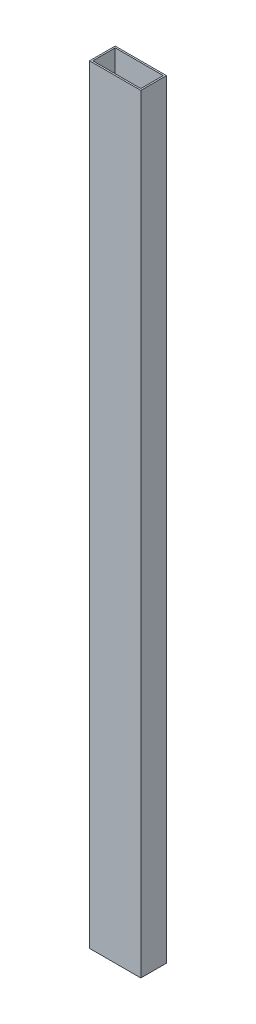
SolidWorks part; units mm, degrees
ref_plane "Front Plane" through (0, 0, 0) normal (0, 0, 1) x (1, 0, 0)
ref_plane "Top Plane" through (0, 0, 0) normal (0, 1, 0) x (1, 0, 0)
ref_plane "Right Plane" through (0, 0, 0) normal (1, 0, 0) x (0, 0, -1)
sketch "Sketch1" plane through (0, 0, 0) normal (0, 1, 0) x (1, 0, 0)
  line L0 (-23.8252, 11.1252) -> (-23.8252, 12.7) construction
  line L1 (-25.4, -12.7) -> (25.4, -12.7)
  line L2 (-25.4, -12.7) -> (-25.4, 12.7)
  line L3 (-25.4, 12.7) -> (25.4, 12.7)
  line L4 (25.4, -12.7) -> (25.4, 12.7)
  line L5 (-25.4, -12.7) -> (25.4, 12.7) construction
  line L6 (-25.4, 12.7) -> (25.4, -12.7) construction
  line L7 (-23.8252, -11.1252) -> (23.8252, -11.1252)
  line L8 (-23.8252, -11.1252) -> (-23.8252, 11.1252)
  line L9 (-23.8252, 11.1252) -> (23.8252, 11.1252)
  line L10 (23.8252, -11.1252) -> (23.8252, 11.1252)
  line L11 (-23.8252, -11.1252) -> (23.8252, 11.1252) construction
  line L12 (-23.8252, 11.1252) -> (23.8252, -11.1252) construction
  line L13 (-23.8252, 11.1252) -> (-25.4, 11.1252) construction
  point P0 (0, 0)
  point P6 (0, 0)
  dimension "D1" = 1.5748
  dimension "D2" = 50.8
  dimension "D3" = 25.4
extrude "Boss-Extrude1" add sketch "Sketch1" along normal blind 762
